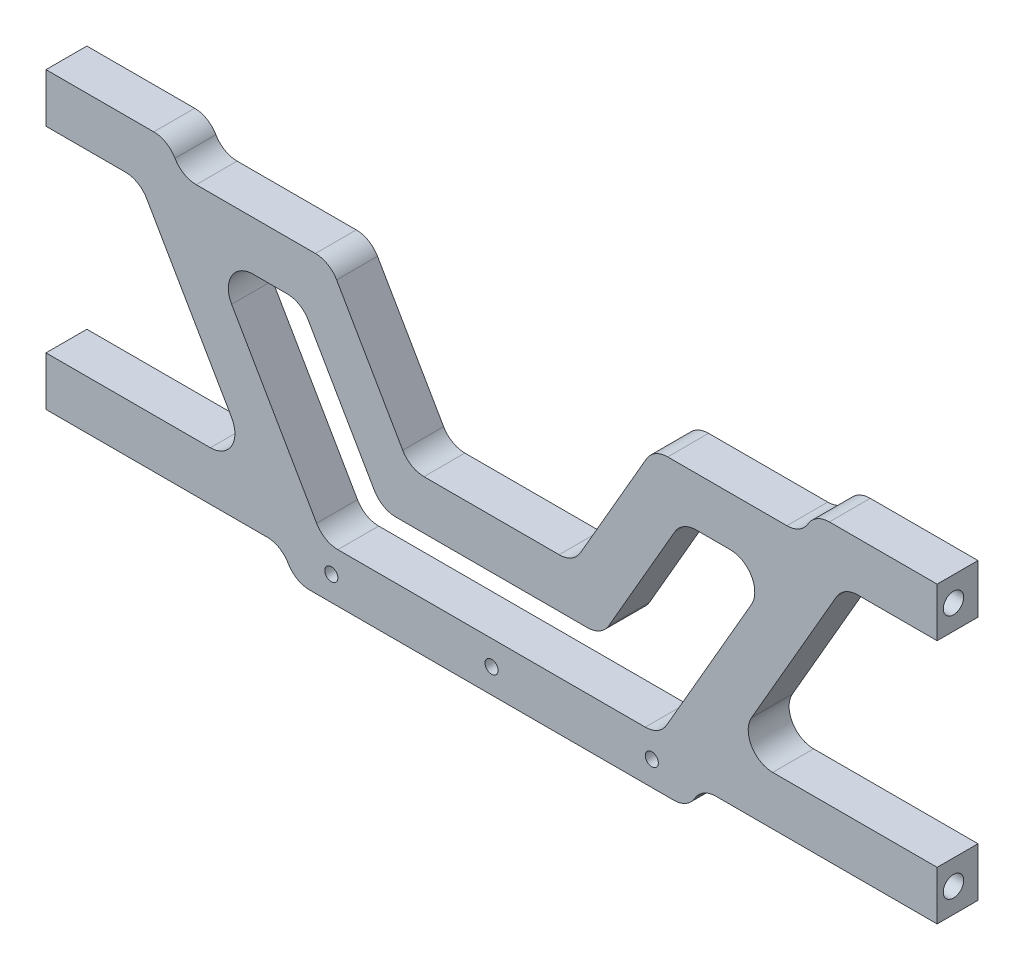
SolidWorks part; units mm, degrees
ref_plane "Front Plane" through (0, 0, 0) normal (0, 0, 1) x (1, 0, 0)
ref_plane "Top Plane" through (0, 0, 0) normal (0, 1, 0) x (1, 0, 0)
ref_plane "Right Plane" through (0, 0, 0) normal (1, 0, 0) x (0, 0, -1)
sketch "Sketch1" plane through (0, 0, 0) normal (0, 0, 1) x (1, 0, 0)
  line L1 (-54.5, 0) -> (54.5, 0)
  line L2 (-54.5, 0) -> (-54.5, 39)
  line L3 (-54.5, 39) -> (54.5, 39)
  line L4 (54.5, 0) -> (54.5, 39)
  dimension "D1" = 39
  dimension "D2" = 109
extrude "Boss-Extrude1" add sketch "Sketch1" along normal blind 5
sketch "Sketch2" plane through (0, 0, 5) normal (0, 0, 1) x (1, 0, 0)
  line L0 (-54.5, 33) -> (-43.0526, 33)
  line L2 (-54.5, 39) -> (-54.5, 0) construction
  line L3 (-43.0526, 33) -> (-29.1962, 9)
  line L5 (-29.1962, 9) -> (-54.5, 9)
  line L6 (-54.5, 9) -> (-54.5, 33)
  line L7 (54.5, 39) -> (-54.5, 39) construction
  line L8 (-39.5885, 39) -> (-37.8564, 36)
  line L9 (-10, 19) -> (0, 19)
  line L10 (0, 19) -> (0, 39)
  line L11 (0, 39) -> (-39.5885, 39)
  line L12 (-54.5, 3) -> (-25.7321, 3)
  line L13 (-25.7321, 3) -> (-24, 0)
  line L14 (-54.5, 0) -> (54.5, 0) construction
  line L15 (-24, 0) -> (-54.5, 0)
  line L16 (-54.5, 0) -> (-54.5, 3)
  line L17 (-13.4641, 13) -> (0, 13)
  line L18 (0, 13) -> (0, 6)
  line L19 (0, 6) -> (-20.5359, 6)
  line L20 (-20.5359, 6) -> (-34.3923, 30)
  line L21 (-37.8564, 36) -> (-19.815, 36)
  line L22 (-19.815, 36) -> (-10, 19)
  line L23 (-13.4641, 13) -> (-23.2791, 30)
  line L24 (-23.2791, 30) -> (-34.3923, 30)
  dimension "D3" = 60
  dimension "D1" = 6
  dimension "D2" = 24
  dimension "D4" = 6
  dimension "D5" = 3
  dimension "D6" = 24
  dimension "D7" = 6
  dimension "D8" = 6
  dimension "D9" = 3
  dimension "D10" = 6
  dimension "D11" = 6
  dimension "D12" = 20
  dimension "D13" = 10
extrude "Cut-Extrude1" cut sketch "Sketch2" against normal up to next
hole_wizard "Tap Drill for M3 Tap1" positions "Sketch4" profile "Sketch3" hole size "M3" standard "ISO"
sketch "Sketch4" plane through (-54.5, 0, 0) normal (-1, 0, 0) x (0, 0, 1)
  line L0 (5, 39) -> (0, 39) construction
  line L4 (0, 9) -> (0, 3) construction
  point P0 (3, 36)
  point P2 (3, 6)
  dimension "D1" = 3
  dimension "D2" = 30
  dimension "D3" = 3
sketch "Sketch3" plane through (-54.5, 36, 3) normal (0, 1, 0) x (0, 0, 1)
  line L0 (0, 0) -> (0, 10.7511)
  line L1 (0, 10.7511) -> (1.25, 10)
  line L2 (1.25, 10) -> (1.25, 0)
  line L5 (1.25, 0) -> (0, 0)
  line L10 (0, 10.7511) -> (-1.25, 10) construction
  line L11 (0, -6.35) -> (0, 107.95) construction
  dimension "Hole Dia." = 2.5
  dimension "Hole Depth" = 10
  dimension "Drill Angle" = 118
fillet "Fillet1" radius 3 12 edges at (-43.0526, 33, 2.5) (-29.1962, 9, 2.5) (-24, 0, 2.5) (-25.7321, 3, 2.5) (-39.5885, 39, 2.5) (-20.5359, 6, 2.5) (-37.8564, 36, 2.5) (-23.2791, 30, 2.5) (-19.815, 36, 2.5) (-34.3923, 30, 2.5) (-10, 19, 2.5) (-13.4641, 13, 2.5)
mirror "Mirror1" about plane through (0, 0, 0) normal (1, 0, 0) of "Fillet1", "Tap Drill for M3 Tap1", "Cut-Extrude1"
hole_wizard "Tap Drill for M2 Tap1" positions "Sketch7" profile "Sketch6" hole size "M2" standard "ISO" end condition up to next
sketch "Sketch7" plane through (0, 0, 5) normal (0, 0, 1) x (1, 0, 0)
  line L0 (-22.2679, 0) -> (22.2679, 0) construction
  point P0 (-19.6, 3)
  point P2 (0, 3)
  point P4 (19.6, 3)
  dimension "D1" = 19.6
  dimension "D2" = 19.6
  dimension "D3" = 3
sketch "Sketch6" plane through (-19.6, 3, 5) normal (1, 0, 0) x (0, -1, 0)
  line L0 (0, 0) -> (0, 5)
  line L1 (0, 5) -> (0.8, 5)
  line L2 (0.8, 5) -> (0.8, 0)
  line L5 (0.8, 0) -> (0, 0)
  line L11 (0, -6.35) -> (0, 107.95) construction
  dimension "Thru Hole Dia." = 1.6
  dimension "Thru Hole Depth" = 5
